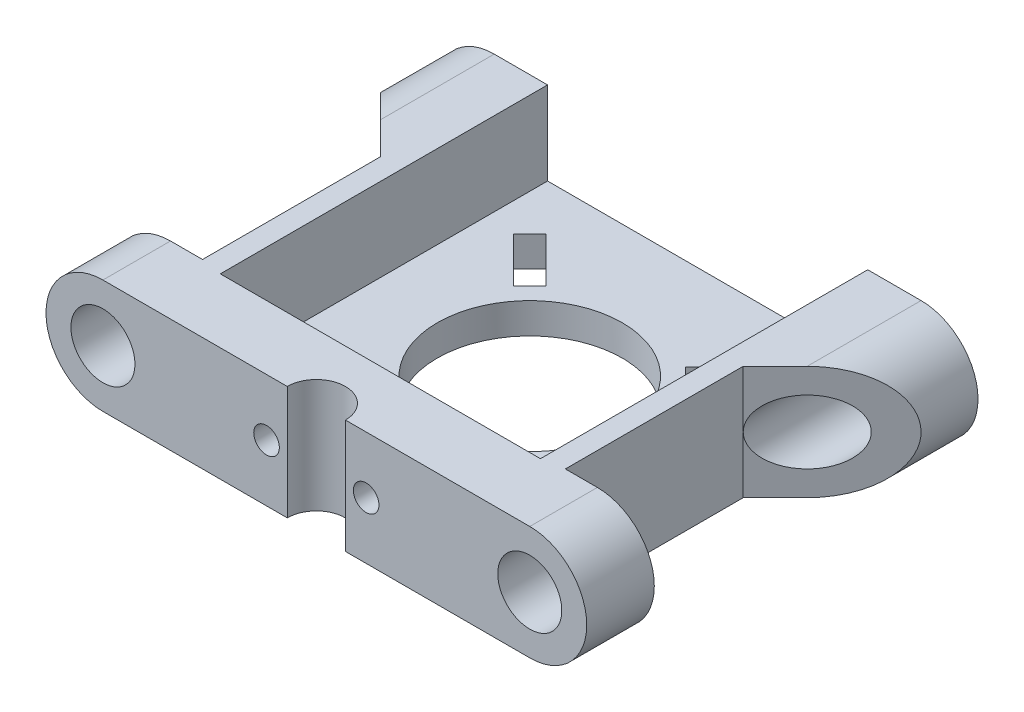
SolidWorks part; units mm, degrees
ref_plane "Piano frontale" through (0, 0, 0) normal (0, 0, 1) x (1, 0, 0)
ref_plane "Piano superiore" through (0, 0, 0) normal (0, 1, 0) x (1, 0, 0)
ref_plane "Piano destro" through (0, 0, 0) normal (1, 0, 0) x (0, 0, -1)
sketch "Schizzo1" plane through (0, 0, 0) normal (0, 0, 1) x (1, 0, 0)
  line L0 (-30, 0) -> (30, 0) construction
  line L1 (-30, -8) -> (30, -8)
  line L2 (0, 8) -> (0, -8) construction
  line L3 (-30, 8) -> (30, 8)
  arc A0 (-30, 8) -> (-30, -8) centre (-30, 0) ccw
  circle A1 centre (-30, 0) radius 4.5
  circle A2 centre (30, 0) radius 4.5
  arc A3 (30, 8) -> (30, -8) centre (30, 0) cw
  point P4 (0, 0)
  dimension "D2" = 16
  dimension "D3" = 9
  dimension "D1" = 30
extrude "Base" add sketch "Schizzo1" along normal mid plane 55
sketch "Schizzo3" plane through (0, 8, 0) normal (0, 1, 0) x (1, 0, 0)
  line L0 (13, 2.5) -> (-13, 2.5) construction
  line L1 (16.1927, 20.9555) -> (12.0915, 12.3288) construction
  line L2 (9.8288, 14.5915) -> (18.4555, 18.6927) construction
  line L3 (12.0915, 12.3288) -> (18.4555, 18.6927)
  line L4 (16.1927, 20.9555) -> (18.4555, 18.6927)
  line L5 (9.8288, 14.5915) -> (12.0915, 12.3288)
  line L6 (9.8288, 14.5915) -> (16.1927, 20.9555)
  line L7 (9.8288, -9.5915) -> (18.4555, -13.6927) construction
  line L8 (38, -27.5) -> (38, -18)
  line L9 (38, -27.5) -> (38, 27.5) construction
  line L10 (38, -18) -> (25.5, -18)
  line L11 (25.5, -18) -> (25.5, 7)
  line L12 (25.5, -27.5) -> (25.5, -18) construction
  line L13 (25.5, 7) -> (38, 19.5)
  line L14 (38, 19.5) -> (38, -18)
  line L15 (16.1927, -15.9555) -> (12.0915, -7.3288) construction
  line L16 (0, 27.5) -> (0, -27.5) construction
  line L17 (30, 27.5) -> (-30, 27.5) construction
  line L18 (30, -27.5) -> (-30, -27.5) construction
  line L19 (-38, 19.5) -> (-38, -18)
  line L20 (-25.5, 7) -> (-38, 19.5)
  line L21 (-25.5, -18) -> (-25.5, 7)
  line L22 (-38, -18) -> (-25.5, -18)
  line L23 (-38, -27.5) -> (-38, -18)
  line L24 (0, 2.5) -> (-14.1421, 16.6421) construction
  line L25 (-9.8288, 14.5915) -> (-16.1927, 20.9555)
  line L26 (-9.8288, 14.5915) -> (-12.0915, 12.3288)
  line L27 (-16.1927, 20.9555) -> (-18.4555, 18.6927)
  line L28 (-12.0915, 12.3288) -> (-18.4555, 18.6927)
  line L29 (-9.8288, 14.5915) -> (-18.4555, 18.6927) construction
  line L30 (-16.1927, 20.9555) -> (-12.0915, 12.3288) construction
  line L31 (9.8288, -9.5915) -> (16.1927, -15.9555)
  line L32 (9.8288, -9.5915) -> (12.0915, -7.3288)
  line L33 (16.1927, -15.9555) -> (18.4555, -13.6927)
  line L34 (12.0915, -7.3288) -> (18.4555, -13.6927)
  line L35 (-16.1927, -15.9555) -> (-12.0915, -7.3288) construction
  line L36 (-9.8288, -9.5915) -> (-18.4555, -13.6927) construction
  line L37 (-12.0915, -7.3288) -> (-18.4555, -13.6927)
  line L38 (-16.1927, -15.9555) -> (-18.4555, -13.6927)
  line L39 (-9.8288, -9.5915) -> (-12.0915, -7.3288)
  line L40 (-9.8288, -9.5915) -> (-16.1927, -15.9555)
  line L41 (25.5, -27.5) -> (34.5, -27.5) construction
  line L42 (25.5, -27.5) -> (34.5, -27.5)
  line L43 (4.09, -27.5) -> (-4.09, -27.5)
  circle A0 centre (0, 2.5) radius 13
  arc A1 (-4.09, -27.5) -> (4.09, -27.5) centre (0, -27.5) cw
  point P26 (0, 2.5)
  line M14 (-30, -27.5) -> (30, -27.5)
  line M15 (30, -27.5) -> (30, 27.5)
  dimension "D4" = 26
  dimension "D1" = 9.5
  dimension "D2" = 25
  dimension "D3" = 135
  dimension "D5" = 45
  dimension "D6" = 3.2
  dimension "D7" = 9
  dimension "D8" = 15.5
  dimension "D9" = 25
  dimension "D10" = 8.18
extrude "Holes" cut sketch "Schizzo3" against normal through all contours L13 L11 L10 M15 | L14 L13 L10 M15 | A0 | A1 M14 | L3 L4 L6 L5 | L25 L27 L28 L26 | L22 L21 L20 L19 | L40 L38 L37 L39 | L31 L33 L34 L32 region at (0, 8, 25.7642) region at (34.1592, 8, 1.1704) region at (27.8119, 8, 4.344) region at (0, 8, -2.5)
sketch "Schizzo5" plane through (0, 8, 0) normal (0, 1, 0) x (1, 0, 0)
  line L0 (22.5, 27.5) -> (22.5, -18.5)
  line L1 (30, 27.5) -> (-30, 27.5) construction
  line L2 (22.5, -18.5) -> (-22.5, -18.5)
  line L3 (-22.5, -18.5) -> (-22.5, 27.5)
  line L4 (-22.5, 0) -> (22.5, 0) construction
  line L5 (-25.5, -18) -> (-25.5, 7) construction
  line L6 (30, -27.5) -> (4.09, -27.5) construction
  line L7 (22.5, 27.5) -> (-22.5, 27.5)
  point P10 (0, 0)
  dimension "D1" = 3
  dimension "D2" = 9
extrude "Flange" cut sketch "Schizzo5" against normal blind 11.7
sketch "Schizzo6" plane through (0, 0, 27.5) normal (0, 0, 1) x (1, 0, 0)
  line L0 (0, -8) -> (0, 8) construction
  line L3 (4.09, -8) -> (-4.09, -8) construction
  line L4 (4.09, 8) -> (-4.09, 8) construction
  line L5 (-38, 0) -> (38, 0) construction
  arc A0 (-30, 8) -> (-30, -8) centre (-30, 0) ccw construction
  arc A1 (30, -8) -> (30, 8) centre (30, 0) ccw construction
  circle A2 centre (7, 0) radius 1.8
  circle A3 centre (-7, 0) radius 1.8
  dimension "D1" = 3.6
  dimension "D2" = 7
extrude "Screw holes" cut sketch "Schizzo6" against normal up to next
sketch "Schizzo7" plane through (0, 0, 18.5) normal (0, 0, -1) x (-1, 0, 0)
  line L1 (-3.6, 0) -> (-5.3, 2.9445)
  line L2 (-5.3, 2.9445) -> (-8.7, 2.9445)
  line L3 (-8.7, 2.9445) -> (-10.4, 0)
  line L4 (-10.4, 0) -> (-8.7, -2.9445)
  line L5 (-8.7, -2.9445) -> (-5.3, -2.9445)
  line L6 (-5.3, -2.9445) -> (-3.6, 0)
  line L7 (10.4, 0) -> (8.7, 2.9445)
  line L8 (8.7, 2.9445) -> (5.3, 2.9445)
  line L9 (5.3, 2.9445) -> (3.6, 0)
  line L10 (3.6, 0) -> (5.3, -2.9445)
  line L11 (5.3, -2.9445) -> (8.7, -2.9445)
  line L12 (8.7, -2.9445) -> (10.4, 0)
  circle A0 centre (-7, 0) radius 2.9445 construction
  circle A1 centre (7, 0) radius 1.8 construction
  circle A2 centre (7, 0) radius 1.8
  circle A3 centre (7, 0) radius 2.9445 construction
  dimension "D1" = 6.8
  dimension "D2" = 6.8
extrude "Nut holes" cut sketch "Schizzo7" against normal blind 2.4
ref_axis "Motor axis" through (0, -8, -2.5) along (0, 1, 0)
ref_axis "Bar1 clamp" through (-30, 0, -7) along (0, 0, -1)
ref_axis "Bar 2 clamp" through (30, 0, -7) along (0, 0, -1)
